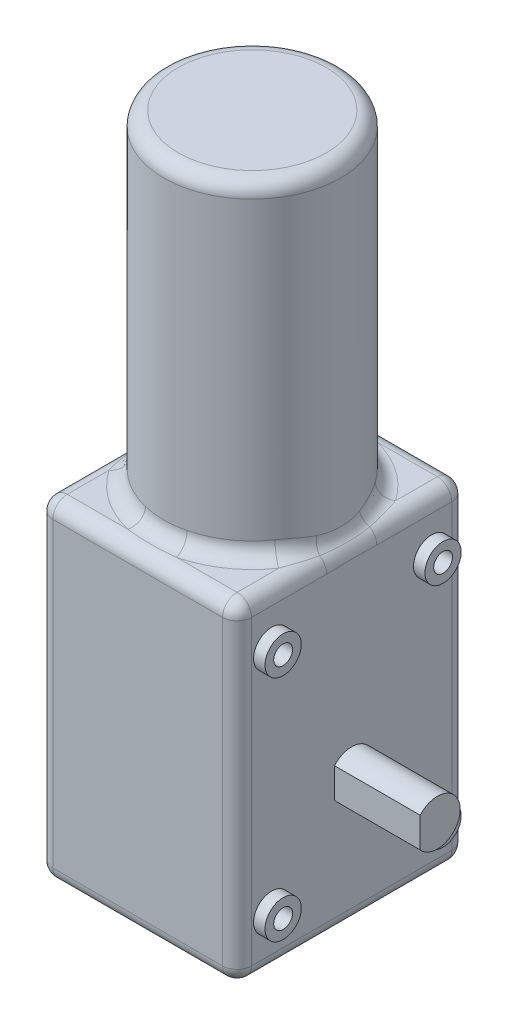
SolidWorks part; units mm, degrees
ref_plane "Front Plane" through (0, 0, 0) normal (0, 0, 1) x (1, 0, 0)
ref_plane "Top Plane" through (0, 0, 0) normal (0, 1, 0) x (1, 0, 0)
ref_plane "Right Plane" through (0, 0, 0) normal (1, 0, 0) x (0, 0, -1)
sketch "Sketch2" plane through (0, 0, 0) normal (0, 1, 0) x (1, 0, 0)
  circle A0 centre (0, 0) radius 15.494
  dimension "D1" = 30.988
extrude "Boss-Extrude1" add sketch "Sketch2" along normal blind 56.896
sketch "Sketch3" plane through (0, 0, 0) normal (0, -1, 0) x (1, 0, 0)
  line L1 (-17.399, 20.066) -> (17.399, 20.066)
  line L2 (-17.399, 20.066) -> (-17.399, -20.066)
  line L3 (-17.399, -20.066) -> (17.399, -20.066)
  line L4 (17.399, 20.066) -> (17.399, -20.066)
  line L5 (-17.399, 20.066) -> (17.399, -20.066) construction
  line L6 (-17.399, -20.066) -> (17.399, 20.066) construction
  point P0 (0, 0)
  dimension "D1" = 40.132
  dimension "D2" = 34.798
extrude "Boss-Extrude2" add sketch "Sketch3" along normal blind 57.912
sketch "Sketch4" plane through (17.399, 0, 0) normal (1, 0, 0) x (0, 0, -1)
  line L0 (20.066, -57.912) -> (-20.066, -57.912) construction
  line L5 (-4, -34.912) -> (-3.0094, -34.912)
  line L6 (-3.0094, -32.2769) -> (-3.0094, -37.5471)
  circle A1 centre (0, -34.912) radius 4
  dimension "D3" = 0.9906
  dimension "D1" = 8
  dimension "D2" = 23
extrude "Boss-Extrude3" add sketch "Sketch4" along normal blind 15 and the other way blind 49.798 contours L6 A1 region at (17.399, -34.912, -0.2613)
fillet "Fillet1" radius 2.54 12 edges at (-17.399, 0, 0) (17.399, -28.956, 20.066) (-17.399, -28.956, 20.066) (0, 0, 20.066) (-17.399, -28.956, -20.066) (17.399, -28.956, -20.066) (0, 0, -20.066) (0, -57.912, -20.066) (-17.399, -57.912, 0) (0, -57.912, 20.066) (17.399, -57.912, 0) (17.399, 0, 0)
fillet "Fillet2" radius 2.54 5 edges at (15.494, 0, 0) (0, 0, 15.494) (-15.494, 0, 0) (0, 0, -15.494) (0, 56.896, 15.494)
sketch "Sketch5" plane through (17.399, 0, 0) normal (1, 0, 0) x (0, 0, -1)
  line L0 (0, -8.956) -> (0, -48.956) construction
  line L1 (-14, -8.956) -> (14, -8.956) construction
  line L2 (-14, -8.956) -> (-14, -48.956) construction
  line L3 (-14, -48.956) -> (14, -48.956) construction
  line L4 (14, -8.956) -> (14, -48.956) construction
  line L5 (-17.526, -28.956) -> (17.526, -28.956) construction
  line L6 (-17.526, -2.54) -> (-17.526, -55.372) construction
  line L7 (17.526, -55.372) -> (17.526, -2.54) construction
  circle A1 centre (-14, -8.956) radius 3.175
  circle A2 centre (14, -8.956) radius 3.175
  circle A3 centre (-14, -48.956) radius 3.175
  circle A4 centre (14, -48.956) radius 3.175
  point P9 (0, -34.912)
  dimension "D4" = 6.35
  dimension "D1" = 40
  dimension "D2" = 28
  dimension "D3" = 20
extrude "Boss-Extrude4" add sketch "Sketch5" along normal blind 2
hole_wizard "Tap Drill for M4x0.7 Tap1" positions "Sketch6" profile "Sketch7" hole size "M4x0.7" standard "ANSI Metric"
sketch "Sketch6" plane through (19.399, 0, 0) normal (1, 0, 0) x (0, 0, -1)
  point P0 (-14, -8.956)
  point P3 (14, -8.956)
  point P6 (-14, -48.956)
  point P9 (14, -48.956)
sketch "Sketch7" plane through (19.399, -8.956, 14) normal (0, 1, 0) x (0, 0, -1)
  line L0 (0, 0) -> (0, 4.9914)
  line L1 (0, 4.9914) -> (1.65, 4)
  line L2 (1.65, 4) -> (1.65, 0)
  line L5 (1.65, 0) -> (0, 0)
  line L10 (0, 4.9914) -> (-1.65, 4) construction
  line L11 (0, -6.35) -> (0, 107.95) construction
  dimension "Hole Dia." = 3.3
  dimension "Hole Depth" = 4
  dimension "Drill Angle" = 118
equation "\"D3@Sketch5\"=\"D1@Sketch5\"/2"
